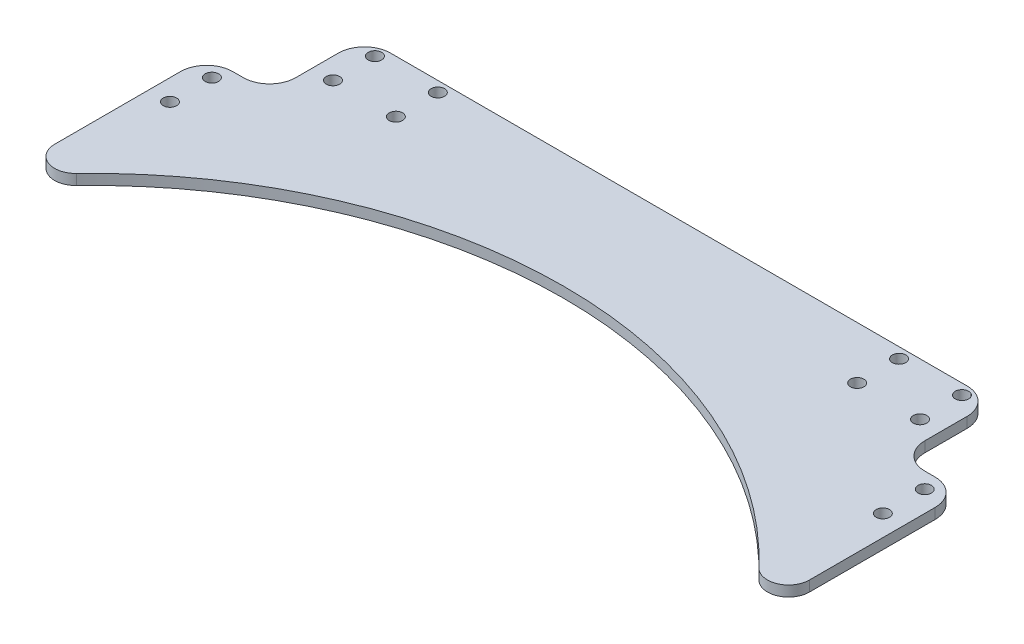
SolidWorks part; units mm, degrees
ref_plane "Front Plane" through (0, 0, 0) normal (0, 0, 1) x (1, 0, 0)
ref_plane "Top Plane" through (0, 0, 0) normal (0, 1, 0) x (1, 0, 0)
ref_plane "Right Plane" through (0, 0, 0) normal (1, 0, 0) x (0, 0, -1)
sketch "Sketch1" plane through (0, 0, 0) normal (0, 1, 0) x (1, 0, 0)
  line L0 (0, 0) -> (0, 92.075)
  line L1 (0, 92.075) -> (228.6, 92.075)
  line L2 (228.6, 92.075) -> (228.6, 0)
  arc A0 (0, 0) -> (228.6, 0) centre (114.3, -85.725) cw
  dimension "D3" = 142.875
  dimension "D1" = 177.8
  dimension "D2" = 228.6
extrude "Boss-Extrude1" add sketch "Sketch1" along normal blind 3.175
sketch "Sketch3" plane through (0, 0, 0) normal (0, -1, 0) x (1, 0, 0)
  line L0 (228.6, -92.075) -> (0, -92.075) construction
  line L1 (114.3, -92.075) -> (114.3, -57.15) construction
  circle A2 centre (25.4, -88.9) radius 2.032 construction
  circle A3 centre (44.45, -88.9) radius 2.032 construction
  arc A8 (0, 0) -> (228.6, 0) centre (114.3, 85.725) ccw construction
  circle A17 centre (25.4, -76.2) radius 2.032 construction
  circle A18 centre (44.45, -76.2) radius 2.032 construction
  circle A19 centre (25.4, -88.9) radius 2.032
  circle A20 centre (44.45, -88.9) radius 2.032
  circle A21 centre (25.4, -76.2) radius 2.032
  circle A22 centre (44.45, -76.2) radius 2.032
  circle A23 centre (184.15, -88.9) radius 2.032
  circle A24 centre (184.15, -76.2) radius 2.032
  circle A25 centre (203.2, -76.2) radius 2.032
  circle A26 centre (203.2, -88.9) radius 2.032
  point P12 (114.3, -92.075)
extrude "Cut-Extrude1" cut sketch "Sketch3" against normal through all
fillet "Fillet1" radius 6.35 2 edges at (0, 1.5875, 0) (228.6, 1.5875, 0)
sketch "Sketch4" plane through (0, 0, 0) normal (0, -1, 0) x (1, 0, 0)
  line L0 (0, -63.3411) -> (19.05, -63.3411)
  line L1 (0, -92.075) -> (0, -17.3036) construction
  line L15 (19.05, -63.3411) -> (19.05, -92.075)
  line L16 (19.05, -92.075) -> (0, -92.075)
  line L17 (0, -92.075) -> (0, -63.3411)
  line L19 (19.05, -70.0557) -> (19.05, 14.5728) construction
  line L21 (209.55, -70.0557) -> (209.55, 14.5728) construction
  line L22 (228.6, -92.075) -> (228.6, -63.3411)
  line L24 (228.6, -63.3411) -> (209.55, -63.3411)
  line L25 (209.55, -63.3411) -> (209.55, -92.075)
  line L26 (228.6, -92.075) -> (0, -92.075) construction
  line L27 (209.55, -92.075) -> (228.6, -92.075)
  circle A0 centre (6.35, -45.8786) radius 2.032
  circle A1 centre (6.35, -58.5786) radius 2.032
  circle A3 centre (222.25, -45.8786) radius 2.032
  circle A4 centre (222.25, -58.5786) radius 2.032
  arc A6 (10.9436, -12.9194) -> (0, -17.3036) centre (6.35, -17.3036) ccw construction
  arc A7 (10.9436, -12.9194) -> (0, -17.3036) centre (6.35, -17.3036) ccw construction
  arc A8 (228.6, -17.3036) -> (217.6564, -12.9194) centre (222.25, -17.3036) ccw construction
  arc A9 (228.6, -17.3036) -> (217.6564, -12.9194) centre (222.25, -17.3036) ccw construction
  line M8 (0, -17.3036) -> (0, -92.075)
  line M9 (0, -92.075) -> (228.6, -92.075)
  line M10 (228.6, -92.075) -> (228.6, -17.3036)
  dimension "D2" = 4.064
  dimension "D1" = 12.7
  dimension "D3" = 28.575
  dimension "D4" = 4.7625
extrude "Cut-Extrude2" cut sketch "Sketch4" against normal through all contours A0 | A1 | A3 | A4 | L15 L0 M8 M9 | L24 L25 M9 M10 region at (219.075, 0, -77.7081) region at (9.525, 0, -77.7081) region at (6.35, 0, -45.8786) region at (6.35, 0, -58.5786) region at (222.25, 0, -45.8786) region at (222.25, 0, -58.5786)
fillet "Fillet2" radius 7.9375 6 edges at (209.55, 1.5875, -92.075) (209.55, 1.5875, -63.3411) (228.6, 1.5875, -63.3411) (19.05, 1.5875, -92.075) (19.05, 1.5875, -63.3411) (0, 1.5875, -63.3411)
